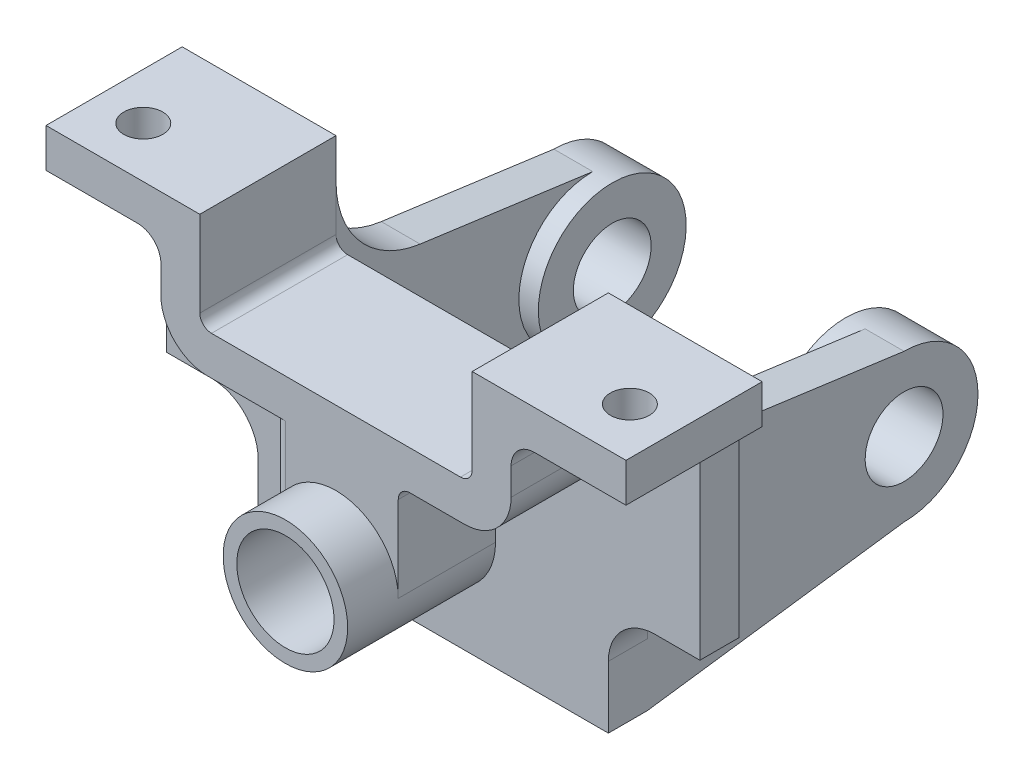
SolidWorks part; units mm, degrees
note: The reader was unsure of these and kept them because the rebuilt part matched: shared geometry of "Sketch1<4>", "Sketch1<12>", "Sketch6<6>".
ref_plane "Front Plane" through (0, 0, 0) normal (0, 0, 1) x (1, 0, 0)
ref_plane "Top Plane" through (0, 0, 0) normal (0, 1, 0) x (1, 0, 0)
ref_plane "Right Plane" through (0, 0, 0) normal (1, 0, 0) x (0, 0, -1)
sketch "Sketch1" plane through (0, 0, 0) normal (0, 0, 1) x (1, 0, 0)
  line L0 (-45, 0) -> (45, 0)
  line L1 (0, 0) -> (0, 88) construction
  line L2 (0, 63) -> (35, 63)
  line L3 (35, 63) -> (35, 88)
  line L4 (35, 88) -> (74.5302, 88)
  line L5 (16, 53) -> (45, 53)
  line L6 (45, 53) -> (45, 78)
  line L7 (45, 78) -> (74.5302, 78)
  line L8 (45, 0) -> (45, 28)
  line L9 (45, 28) -> (68.5302, 28)
  line L10 (68.5302, 28) -> (68.5302, 78)
  line L11 (74.5302, 88) -> (74.5302, 78)
  line L12 (16, 28) -> (16, 53)
  line L13 (0, 53) -> (45, 53) construction
  line L14 (-45, 0) -> (-45, 28)
  line L15 (-45, 28) -> (-68.5302, 28)
  line L16 (-68.5302, 28) -> (-68.5302, 78)
  line L17 (-16, 28) -> (-16, 53)
  line L18 (-16, 53) -> (-45, 53)
  line L19 (-45, 53) -> (-45, 78)
  line L20 (-45, 78) -> (-74.5302, 78)
  line L21 (-74.5302, 88) -> (-74.5302, 78)
  line L22 (-35, 88) -> (-74.5302, 88)
  line L23 (-35, 63) -> (-35, 88)
  line L24 (0, 63) -> (-35, 63)
  circle A0 centre (0, 28) radius 16
  circle A1 centre (0, 28) radius 12.5
  dimension "D3" = 25
  dimension "D4" = 32
  dimension "D1" = 90
  dimension "D2" = 88
  dimension "D5" = 60
  dimension "D6" = 10
  dimension "D7" = 6
extrude "Boss-Extrude1" add sketch "Sketch1" along normal blind 10 contours A0 L12 L5 L6 L7 L11 L4 L3 L2 L24 L23 L22 L21 L20 L19 L18 L17 | A0 A1 | A0 L17 L18 L19 L20 L16 L15 L14 L0 L8 L9 L10 L7 L6 L5 L12
extrude "Boss-Extrude2" add sketch "Sketch1<4>" along normal blind 35 contours A0 L12 L5 L6 L7 L11 L4 L3 L2 L24 L23 L22 L21 L20 L19 L18 L17 | A0 A1
sketch "Sketch1<4>" plane through (0, 0, 0) normal (0, 0, 1) x (1, 0, 0) same geometry as "Sketch1"
extrude "Boss-Extrude8" add sketch "Sketch1<12>" along normal blind 48 contours A1 | A0
sketch "Sketch1<12>" plane through (0, 0, 0) normal (0, 0, 1) x (1, 0, 0) same geometry as "Sketch1"
sketch "Sketch6" plane through (45, 0, 0) normal (1, 0, 0) x (0, 0, -1)
  line L0 (0, 28) -> (66, 28) construction
  line L1 (0, 0) -> (66, 9)
  line L2 (0, 56) -> (66, 47)
  line L3 (0, 56) -> (0, 0)
  circle A0 centre (66, 28) radius 19
  circle A1 centre (66, 28) radius 10
  dimension "D2" = 20
  dimension "D3" = 38
  dimension "D1" = 66
extrude "Boss-Extrude15" add sketch "Sketch6" against normal blind 10
extrude "Boss-Extrude16" add sketch "Sketch6<6>" against normal blind 15
sketch "Sketch6<6>" plane through (45, 0, 0) normal (1, 0, 0) x (0, 0, -1) same geometry as "Sketch6"
mirror "Mirror1" about plane through (0, 0, 0) normal (1, 0, 0) of "Boss-Extrude15", "Boss-Extrude16"
fillet "Fillet1" radius 25 2 edges at (-40, 56, 0) (40, 56, 0)
fillet "Fillet2" radius 12 4 edges at (-45, 28, 5) (45, 28, 5) (45, 53, 22.5) (-45, 53, 22.5)
fillet "Fillet3" radius 3 4 edges at (35, 63, 17.5) (-35, 63, 17.5) (-16, 40.5, 35) (16, 53, 22.5)
fillet "Fillet5" radius 6 4 edges at (-68.5302, 78, 5) (68.5302, 78, 5) (45, 78, 22.5) (-45, 78, 22.5)
sketch "Sketch7" plane through (0, 78, 0) normal (0, -1, 0) x (1, 0, 0)
  line L0 (74.5302, 10) -> (51, 10) construction
  line L1 (74.5302, 35) -> (74.5302, 10) construction
  circle A0 centre (62.5302, 22) radius 5
  dimension "D1" = 10
  dimension "D2" = 12
  dimension "D3" = 12
extrude "Cut-Extrude1" cut sketch "Sketch7" against normal through all both and the other way through all
mirror "Mirror2" about plane through (0, 0, 0) normal (1, 0, 0) of "Cut-Extrude1"
